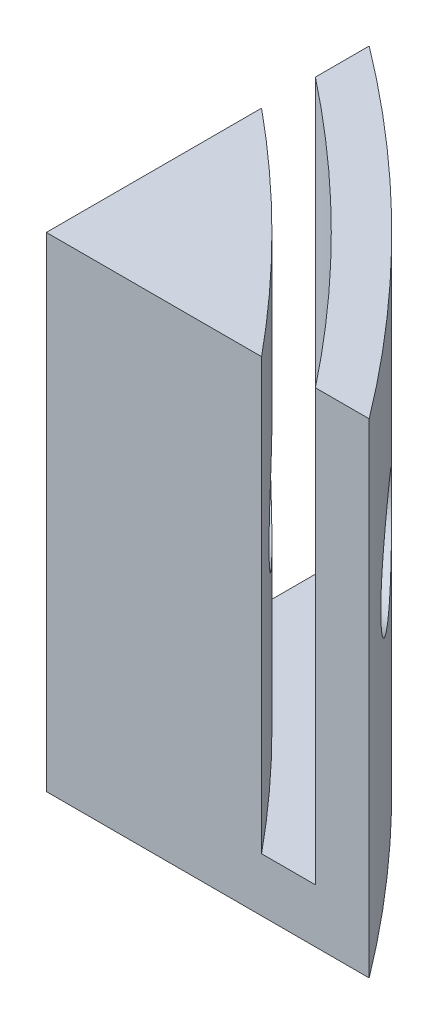
SolidWorks part; units mm, degrees
ref_plane "Front Plane" through (0, 0, 0) normal (0, 0, 1) x (1, 0, 0)
ref_plane "Top Plane" through (0, 0, 0) normal (0, 1, 0) x (1, 0, 0)
ref_plane "Right Plane" through (0, 0, 0) normal (1, 0, 0) x (0, 0, -1)
sketch "Sketch2" plane through (0, 0, 0) normal (0, 1, 0) x (1, 0, 0)
  line L2 (0, 0) -> (12.7, 0)
  line L3 (0, 0) -> (0, 12.7)
  line L4 (0, 0) -> (0, 15.875)
  line L5 (0, 0) -> (15.875, 0)
  line L6 (0, 0) -> (0, 19.05)
  line L7 (0, 0) -> (19.05, 0)
  arc A0 (0, 12.7) -> (12.7, 0) centre (-59.5743, -59.5743) cw
  arc A1 (0, 15.875) -> (15.875, 0) centre (-58.9451, -58.9451) cw
  arc A2 (0, 19.05) -> (19.05, 0) centre (-58.2837, -58.2837) cw
  dimension "D1" = 93.6625
  dimension "D5" = 95.25
  dimension "D6" = 96.8375
  dimension "D2" = 12.7
  dimension "D3" = 15.875
  dimension "D4" = 19.05
extrude "Boss-Extrude1" add sketch "Sketch2" along normal blind 28.575 contours A0 L3 L2 | A1 L4 A0 L5 | A2 L6 A1 L7 region at (4.3682, 0, -4.3682) region at (7.4342, 0, -7.4342) region at (9.1365, 0, -9.1365)
sketch "Sketch3" plane through (0, 28.575, 0) normal (0, 1, 0) x (1, 0, 0)
  line L0 (0, 0) -> (15.875, 0) construction
  line L1 (0, 0) -> (0, 15.875) construction
  line L2 (12.7, 0) -> (15.875, 0)
  line L3 (0, 12.7) -> (0, 15.875)
  arc A0 (12.7, 0) -> (0, 12.7) centre (-59.5743, -59.5743) ccw construction
  arc A1 (15.875, 0) -> (0, 15.875) centre (-58.9451, -58.9451) ccw construction
  arc A2 (12.7, 0) -> (0, 12.7) centre (-59.5743, -59.5743) ccw
  arc A3 (15.875, 0) -> (0, 15.875) centre (-58.9451, -58.9451) ccw
extrude "Cut-Extrude1" cut sketch "Sketch3" against normal blind 25.4
sketch "Sketch4" plane through (0, 0, 0) normal (-1, 0, 0) x (0, 0, 1)
  line L0 (0, 15.875) -> (-12.7889, 15.875) construction
  line L3 (0, 28.575) -> (0, 0) construction
  line L4 (0, 0) -> (-19.05, 0) construction
  circle A0 centre (-6.3945, 15.875) radius 3.175
  dimension "D1" = 15.875
extrude "Cut-Extrude2" cut sketch "Sketch4" against normal through all
